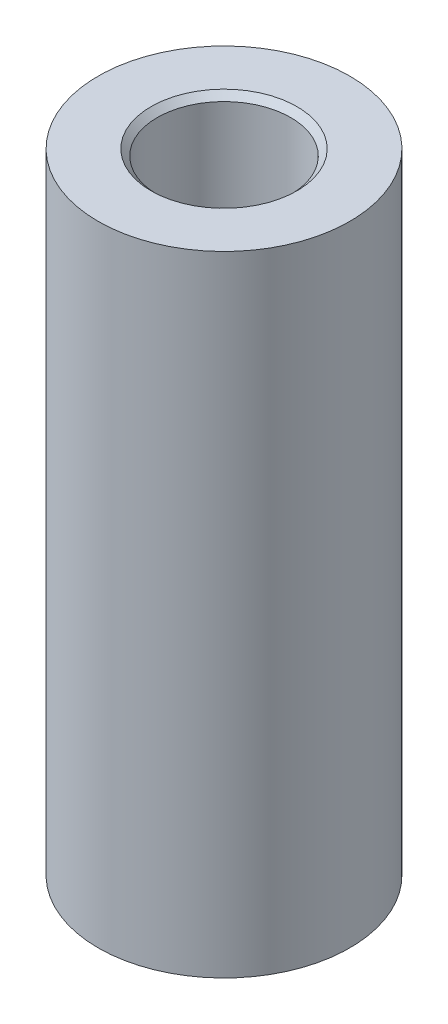
SolidWorks part; units mm, degrees
material "AISI 1045 Steel, cold drawn"
ref_plane "Front Plane" through (0, 0, 0) normal (0, 0, 1) x (1, 0, 0)
ref_plane "Top Plane" through (0, 0, 0) normal (0, 1, 0) x (1, 0, 0)
ref_plane "Right Plane" through (0, 0, 0) normal (1, 0, 0) x (0, 0, -1)
sketch "Sketch1" plane through (0, 0, 0) normal (0, 1, 0) x (1, 0, 0)
  circle A0 centre (0, 0) radius 5
  dimension "D1" = 10
extrude "Boss-Extrude1" add sketch "Sketch1" along normal mid plane 25
hole_wizard "M5 Clearance Hole1" positions "Sketch2" profile "Sketch3" hole size "M5" standard "ANSI Metric" end condition through all
sketch "Sketch2" plane through (0, 12.5, 0) normal (0, 1, 0) x (1, 0, 0)
  point P0 (0, 0)
sketch "Sketch3" plane through (0, 12.5, 0) normal (1, 0, 0) x (0, 0, 1)
  line L0 (0, 0) -> (0, 25)
  line L1 (0, 25) -> (2.65, 25)
  line L2 (2.65, 25) -> (2.65, 0)
  line L5 (2.65, 0) -> (0, 0)
  line L11 (0, -6.35) -> (0, 107.95) construction
  dimension "Thru Hole Dia." = 5.3
  dimension "Thru Hole Depth" = 25
chamfer "Chamfer1" distance 0.25 angle 45 2 edges at (0, 12.5, 2.65) (0, -12.5, 2.65)
